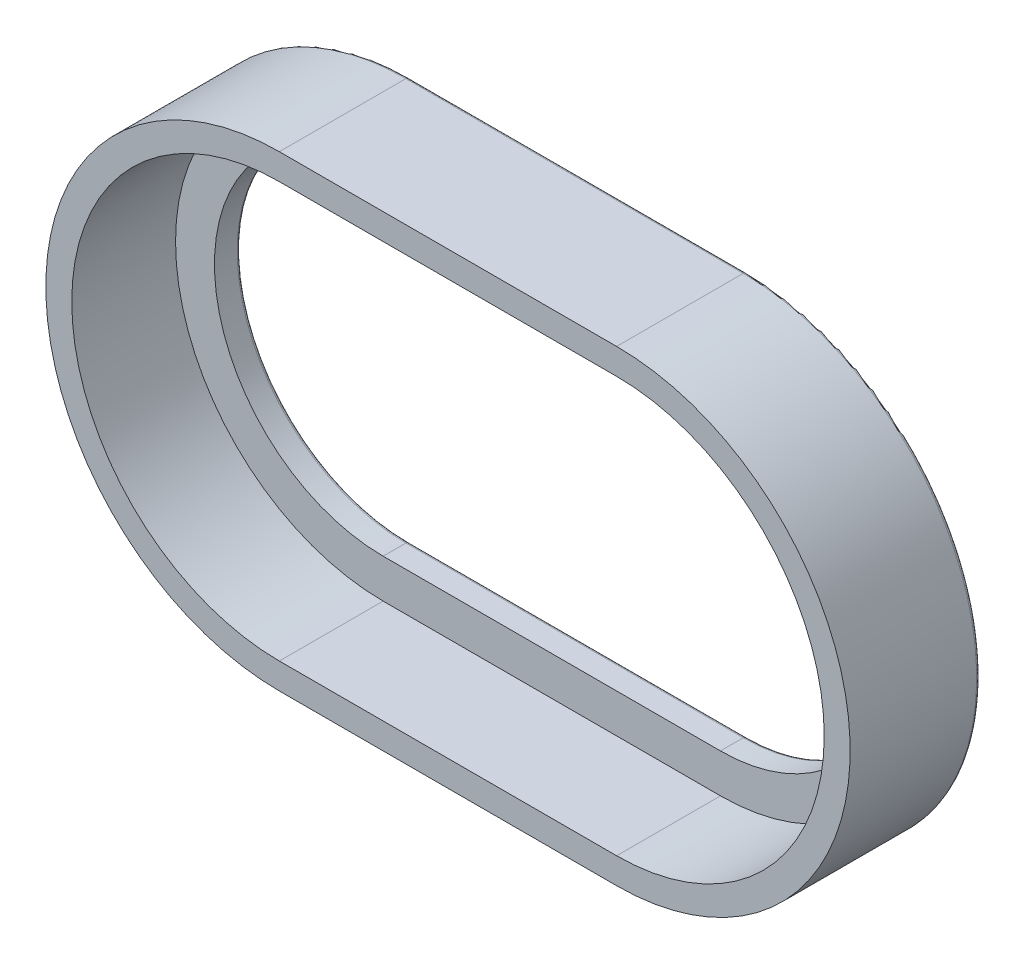
SolidWorks part; units mm, degrees
ref_plane "Front Plane" through (0, 0, 0) normal (0, 0, 1) x (1, 0, 0)
ref_plane "Top Plane" through (0, 0, 0) normal (0, 1, 0) x (1, 0, 0)
ref_plane "Right Plane" through (0, 0, 0) normal (1, 0, 0) x (0, 0, -1)
sketch "Sketch1" plane through (0, 0, 0) normal (0, 0, 1) x (1, 0, 0)
  line L0 (0, 0) -> (52, 0) construction
  line L1 (0, 36) -> (52, 36)
  line L2 (0, -36) -> (52, -36)
  line L3 (0, 0) -> (52, 0) construction
  line L4 (0, 26) -> (52, 26)
  line L5 (0, -26) -> (52, -26)
  line L6 (0, 32) -> (52, 32)
  line L7 (0, -32) -> (52, -32)
  line L8 (0, 26) -> (0, -26) construction
  arc A0 (0, 36) -> (0, -36) centre (0, 0) ccw
  arc A1 (52, -36) -> (52, 36) centre (52, 0) ccw
  arc A2 (0, 26) -> (0, -26) centre (0, 0) ccw
  arc A3 (52, -26) -> (52, 26) centre (52, 0) ccw
  arc A4 (52, -32) -> (52, 32) centre (52, 0) ccw
  arc A5 (0, 32) -> (0, -32) centre (0, 0) ccw
  point P3 (26, 0)
  point P8 (26, 0)
  dimension "D1" = 6
  dimension "D3" = 10
  dimension "boxInteriorDiam" = 64
extrude "Boss-Extrude1" add sketch "Sketch1" along normal blind 20 contours L2 A1 L1 A0 A5 L6 A4 L7 region at (26, 34.5661, 0)
extrude "Boss-Extrude2" add sketch "Sketch1<3>" along normal blind 4 contours L6 A5 L7 A4 A3 L5 A2 L4 region at (26, 30.6752, 0)
sketch "Sketch1<3>" plane through (0, 0, 0) normal (0, 0, 1) x (1, 0, 0) same geometry as "Sketch1"
fillet "Fillet1" radius 0.5 8 edges at (26, -26, 0) (-26, 0, 0) (26, 26, 0) (78, 0, 0) (88, 0, 0) (26, 36, 0) (-36, 0, 0) (26, -36, 0)
equation "\"speakerCenterDist\" = 40"
equation "\"speakerDiam\" = 50"
equation "\"boxInteriorDiam\" = 64"
